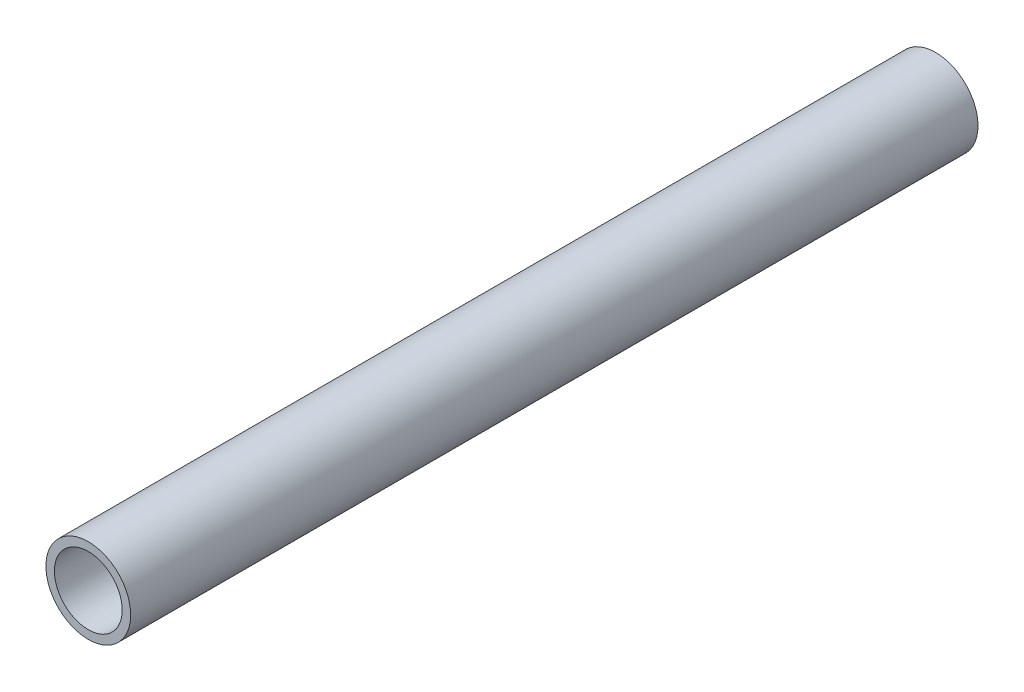
SolidWorks part; units mm, degrees
material "PE Высокой плотности"
ref_plane "Front" through (0, 0, 0) normal (0, 0, 1) x (1, 0, 0)
ref_plane "Top" through (0, 0, 0) normal (0, 1, 0) x (1, 0, 0)
ref_plane "Side" through (0, 0, 0) normal (1, 0, 0) x (0, 0, -1)
sketch "PipeSketch" plane through (0, 0, 0) normal (0, 0, 1) x (1, 0, 0)
  circle A0 centre (0, 0) radius 2.5
  circle A1 centre (0, 0) radius 2
  dimension "OuterDiameter" = 5
  dimension "InnerDiameter" = 4
extrude "Extrusion" add sketch "PipeSketch" along normal blind 50
sketch "FilterSketch" plane through (0, 0, 0) normal (0, 0, 1) x (1, 0, 0)
  circle A0 centre (0, 0) radius 10 construction
  dimension "NominalDiameter" = 20
